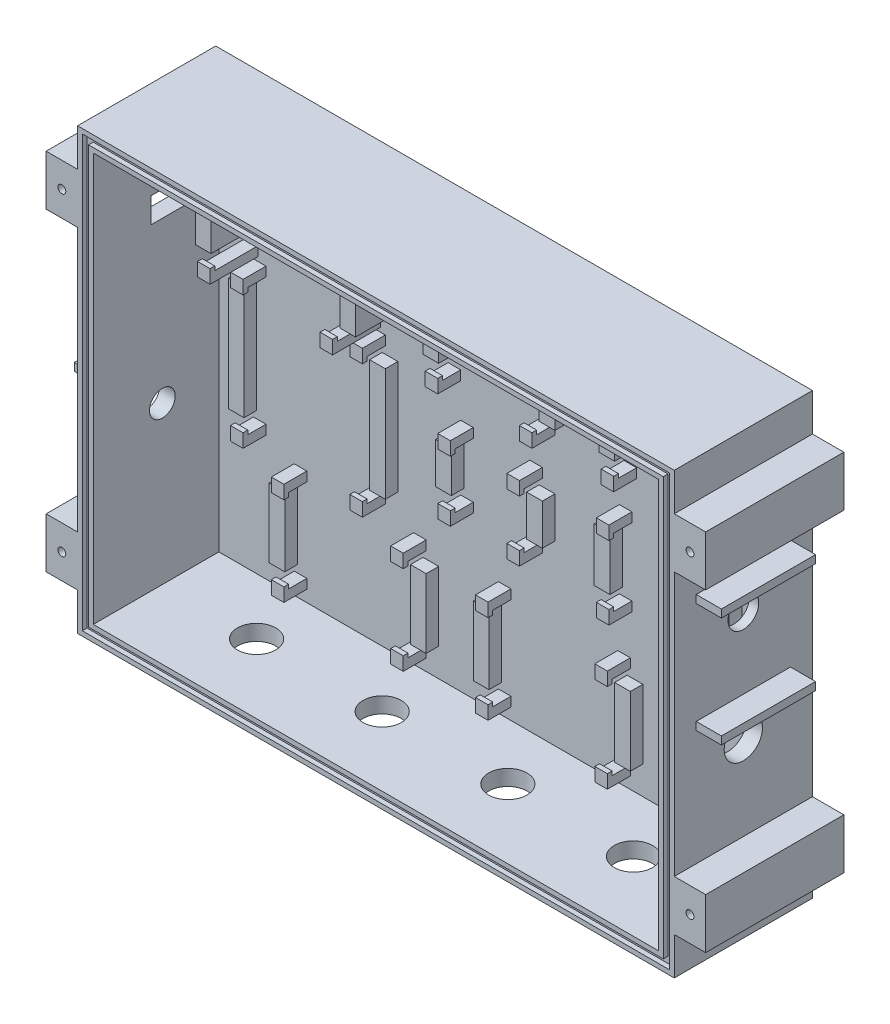
SolidWorks part; units mm, degrees
ref_plane "Front Plane" through (0, 0, 0) normal (0, 0, 1) x (1, 0, 0)
ref_plane "Top Plane" through (0, 0, 0) normal (0, 1, 0) x (1, 0, 0)
ref_plane "Right Plane" through (0, 0, 0) normal (1, 0, 0) x (0, 0, -1)
other "Configuration Table"
sketch "Sketch1" plane through (0, 0, 0) normal (0, 0, 1) x (1, 0, 0)
  line L0 (-95, -70) -> (95, -70)
  line L1 (95, -70) -> (95, 70)
  line L2 (95, 70) -> (-95, 70)
  line L3 (-95, 70) -> (-95, -70)
extrude "Box_Shell" add sketch "Sketch1" along normal blind 44
sketch "Sketch2" plane through (0, 0, 0) normal (0, 0, 1) x (1, 0, 0)
  line L0 (-90, -65) -> (90, -65)
  line L1 (90, -65) -> (90, 65)
  line L2 (90, 65) -> (-90, 65)
  line L3 (-90, 65) -> (-90, -65)
extrude "Box_Cavity" cut sketch "Sketch2" against normal blind 40 from offset 44
sketch "Sketch3" plane through (0, 0, 0) normal (0, 0, 1) x (1, 0, 0)
  line L0 (-105, -58) -> (-95, -58)
  line L1 (-95, -58) -> (-95, -42)
  line L2 (-95, -42) -> (-105, -42)
  line L3 (-105, -42) -> (-105, -58)
  line L4 (-105, 42) -> (-95, 42)
  line L5 (-95, 42) -> (-95, 58)
  line L6 (-95, 58) -> (-105, 58)
  line L7 (-105, 58) -> (-105, 42)
  line L8 (95, -58) -> (105, -58)
  line L9 (105, -58) -> (105, -42)
  line L10 (105, -42) -> (95, -42)
  line L11 (95, -42) -> (95, -58)
  line L12 (95, 42) -> (105, 42)
  line L13 (105, 42) -> (105, 58)
  line L14 (105, 58) -> (95, 58)
  line L15 (95, 58) -> (95, 42)
extrude "Lid_Lugs" add sketch "Sketch3" along normal blind 44
sketch "Sketch4" plane through (0, 0, 0) normal (0, 0, 1) x (1, 0, 0)
  circle A0 centre (-100, -50) radius 1.25
  circle A1 centre (-100, 50) radius 1.25
  circle A2 centre (100, -50) radius 1.25
  circle A3 centre (100, 50) radius 1.25
  dimension "D1" = 2.5
  dimension "D2" = 2.5
  dimension "D3" = 2.5
  dimension "D4" = 2.5
extrude "Lid_Screw_Holes_M3" cut sketch "Sketch4" against normal blind 12 from offset 44
sketch "Sketch5" plane through (0, 0, 0) normal (0, 0, 1) x (1, 0, 0)
  line L0 (-93.5, -68.5) -> (93.5, -68.5)
  line L1 (93.5, -68.5) -> (93.5, 68.5)
  line L2 (93.5, 68.5) -> (-93.5, 68.5)
  line L3 (-93.5, 68.5) -> (-93.5, -68.5)
  line L4 (-91.5, -66.5) -> (91.5, -66.5)
  line L5 (91.5, -66.5) -> (91.5, 66.5)
  line L6 (91.5, 66.5) -> (-91.5, 66.5)
  line L7 (-91.5, 66.5) -> (-91.5, -66.5)
extrude "Lid_Gasket_Groove" cut sketch "Sketch5" against normal blind 1.5 from offset 44
sketch "Sketch6" plane through (0, 0, 0) normal (0, 0, 1) x (1, 0, 0)
  line L0 (-85.5, 28) -> (-80.5, 28)
  line L1 (-80.5, 28) -> (-80.5, 52)
  line L2 (-80.5, 52) -> (-85.5, 52)
  line L3 (-85.5, 52) -> (-85.5, 28)
  line L4 (-39.5, 28) -> (-34.5, 28)
  line L5 (-34.5, 28) -> (-34.5, 52)
  line L6 (-34.5, 52) -> (-39.5, 52)
  line L7 (-39.5, 52) -> (-39.5, 28)
extrude "Pads_ESP32" add sketch "Sketch6" along normal blind 12 from offset 4
sketch "Sketch7" plane through (0, 0, 0) normal (0, 0, 1) x (1, 0, 0)
  line L0 (-81.5, 22.7) -> (-77.5, 22.7)
  line L1 (-77.5, 22.7) -> (-77.5, 25.7)
  line L2 (-77.5, 25.7) -> (-81.5, 25.7)
  line L3 (-81.5, 25.7) -> (-81.5, 22.7)
  line L4 (-81.5, 54.3) -> (-77.5, 54.3)
  line L5 (-77.5, 54.3) -> (-77.5, 57.3)
  line L6 (-77.5, 57.3) -> (-81.5, 57.3)
  line L7 (-81.5, 57.3) -> (-81.5, 54.3)
  line L8 (-42.5, 22.7) -> (-38.5, 22.7)
  line L9 (-38.5, 22.7) -> (-38.5, 25.7)
  line L10 (-38.5, 25.7) -> (-42.5, 25.7)
  line L11 (-42.5, 25.7) -> (-42.5, 22.7)
  line L12 (-42.5, 54.3) -> (-38.5, 54.3)
  line L13 (-38.5, 54.3) -> (-38.5, 57.3)
  line L14 (-38.5, 57.3) -> (-42.5, 57.3)
  line L15 (-42.5, 57.3) -> (-42.5, 54.3)
extrude "Clip_Posts_ESP32" add sketch "Sketch7" along normal blind 15.3 from offset 4
sketch "Sketch8" plane through (0, 0, 0) normal (0, 0, 1) x (1, 0, 0)
  line L0 (-81.5, 25.7) -> (-77.5, 25.7)
  line L1 (-77.5, 25.7) -> (-77.5, 27)
  line L2 (-77.5, 27) -> (-81.5, 27)
  line L3 (-81.5, 27) -> (-81.5, 25.7)
  line L4 (-81.5, 53) -> (-77.5, 53)
  line L5 (-77.5, 53) -> (-77.5, 54.3)
  line L6 (-77.5, 54.3) -> (-81.5, 54.3)
  line L7 (-81.5, 54.3) -> (-81.5, 53)
  line L8 (-42.5, 25.7) -> (-38.5, 25.7)
  line L9 (-38.5, 25.7) -> (-38.5, 27)
  line L10 (-38.5, 27) -> (-42.5, 27)
  line L11 (-42.5, 27) -> (-42.5, 25.7)
  line L12 (-42.5, 53) -> (-38.5, 53)
  line L13 (-38.5, 53) -> (-38.5, 54.3)
  line L14 (-38.5, 54.3) -> (-42.5, 54.3)
  line L15 (-42.5, 54.3) -> (-42.5, 53)
extrude "Clip_Lips_ESP32" add sketch "Sketch8" along normal blind 1.5 from offset 17.8
sketch "Sketch9" plane through (0, 0, 0) normal (0, 0, 1) x (1, 0, 0)
  line L0 (-21, 26) -> (-16, 26)
  line L1 (-16, 26) -> (-16, 54)
  line L2 (-16, 54) -> (-21, 54)
  line L3 (-21, 54) -> (-21, 26)
  line L4 (16, 26) -> (21, 26)
  line L5 (21, 26) -> (21, 54)
  line L6 (21, 54) -> (16, 54)
  line L7 (16, 54) -> (16, 26)
extrude "Pads_TDS" add sketch "Sketch9" along normal blind 4 from offset 4
sketch "Sketch10" plane through (0, 0, 0) normal (0, 0, 1) x (1, 0, 0)
  line L0 (-17, 20.7) -> (-13, 20.7)
  line L1 (-13, 20.7) -> (-13, 23.7)
  line L2 (-13, 23.7) -> (-17, 23.7)
  line L3 (-17, 23.7) -> (-17, 20.7)
  line L4 (-17, 56.3) -> (-13, 56.3)
  line L5 (-13, 56.3) -> (-13, 59.3)
  line L6 (-13, 59.3) -> (-17, 59.3)
  line L7 (-17, 59.3) -> (-17, 56.3)
  line L8 (13, 20.7) -> (17, 20.7)
  line L9 (17, 20.7) -> (17, 23.7)
  line L10 (17, 23.7) -> (13, 23.7)
  line L11 (13, 23.7) -> (13, 20.7)
  line L12 (13, 56.3) -> (17, 56.3)
  line L13 (17, 56.3) -> (17, 59.3)
  line L14 (17, 59.3) -> (13, 59.3)
  line L15 (13, 59.3) -> (13, 56.3)
extrude "Clip_Posts_TDS" add sketch "Sketch10" along normal blind 7.3 from offset 4
sketch "Sketch11" plane through (0, 0, 0) normal (0, 0, 1) x (1, 0, 0)
  line L0 (-17, 23.7) -> (-13, 23.7)
  line L1 (-13, 23.7) -> (-13, 25)
  line L2 (-13, 25) -> (-17, 25)
  line L3 (-17, 25) -> (-17, 23.7)
  line L4 (-17, 55) -> (-13, 55)
  line L5 (-13, 55) -> (-13, 56.3)
  line L6 (-13, 56.3) -> (-17, 56.3)
  line L7 (-17, 56.3) -> (-17, 55)
  line L8 (13, 23.7) -> (17, 23.7)
  line L9 (17, 23.7) -> (17, 25)
  line L10 (17, 25) -> (13, 25)
  line L11 (13, 25) -> (13, 23.7)
  line L12 (13, 55) -> (17, 55)
  line L13 (17, 55) -> (17, 56.3)
  line L14 (17, 56.3) -> (13, 56.3)
  line L15 (13, 56.3) -> (13, 55)
extrude "Clip_Lips_TDS" add sketch "Sketch11" along normal blind 1.5 from offset 9.8
sketch "Sketch12" plane through (0, 0, 0) normal (0, 0, 1) x (1, 0, 0)
  line L0 (35, 27) -> (40, 27)
  line L1 (40, 27) -> (40, 53)
  line L2 (40, 53) -> (35, 53)
  line L3 (35, 53) -> (35, 27)
  line L4 (70, 27) -> (75, 27)
  line L5 (75, 27) -> (75, 53)
  line L6 (75, 53) -> (70, 53)
  line L7 (70, 53) -> (70, 27)
extrude "Pads_ORP" add sketch "Sketch12" along normal blind 4 from offset 4
sketch "Sketch13" plane through (0, 0, 0) normal (0, 0, 1) x (1, 0, 0)
  line L0 (39, 21.7) -> (43, 21.7)
  line L1 (43, 21.7) -> (43, 24.7)
  line L2 (43, 24.7) -> (39, 24.7)
  line L3 (39, 24.7) -> (39, 21.7)
  line L4 (39, 55.3) -> (43, 55.3)
  line L5 (43, 55.3) -> (43, 58.3)
  line L6 (43, 58.3) -> (39, 58.3)
  line L7 (39, 58.3) -> (39, 55.3)
  line L8 (67, 21.7) -> (71, 21.7)
  line L9 (71, 21.7) -> (71, 24.7)
  line L10 (71, 24.7) -> (67, 24.7)
  line L11 (67, 24.7) -> (67, 21.7)
  line L12 (67, 55.3) -> (71, 55.3)
  line L13 (71, 55.3) -> (71, 58.3)
  line L14 (71, 58.3) -> (67, 58.3)
  line L15 (67, 58.3) -> (67, 55.3)
extrude "Clip_Posts_ORP" add sketch "Sketch13" along normal blind 7.3 from offset 4
sketch "Sketch14" plane through (0, 0, 0) normal (0, 0, 1) x (1, 0, 0)
  line L0 (39, 24.7) -> (43, 24.7)
  line L1 (43, 24.7) -> (43, 26)
  line L2 (43, 26) -> (39, 26)
  line L3 (39, 26) -> (39, 24.7)
  line L4 (39, 54) -> (43, 54)
  line L5 (43, 54) -> (43, 55.3)
  line L6 (43, 55.3) -> (39, 55.3)
  line L7 (39, 55.3) -> (39, 54)
  line L8 (67, 24.7) -> (71, 24.7)
  line L9 (71, 24.7) -> (71, 26)
  line L10 (71, 26) -> (67, 26)
  line L11 (67, 26) -> (67, 24.7)
  line L12 (67, 54) -> (71, 54)
  line L13 (71, 54) -> (71, 55.3)
  line L14 (71, 55.3) -> (67, 55.3)
  line L15 (67, 55.3) -> (67, 54)
extrude "Clip_Lips_ORP" add sketch "Sketch14" along normal blind 1.5 from offset 9.8
sketch "Sketch15" plane through (0, 0, 0) normal (0, 0, 1) x (1, 0, 0)
  line L0 (-83, -20) -> (-78, -20)
  line L1 (-78, -20) -> (-78, 16)
  line L2 (-78, 16) -> (-83, 16)
  line L3 (-83, 16) -> (-83, -20)
  line L4 (-38, -20) -> (-33, -20)
  line L5 (-33, -20) -> (-33, 16)
  line L6 (-33, 16) -> (-38, 16)
  line L7 (-38, 16) -> (-38, -20)
extrude "Pads_OPT" add sketch "Sketch15" along normal blind 4 from offset 4
sketch "Sketch16" plane through (0, 0, 0) normal (0, 0, 1) x (1, 0, 0)
  line L0 (-79, -25.3) -> (-75, -25.3)
  line L1 (-75, -25.3) -> (-75, -22.3)
  line L2 (-75, -22.3) -> (-79, -22.3)
  line L3 (-79, -22.3) -> (-79, -25.3)
  line L4 (-79, 18.3) -> (-75, 18.3)
  line L5 (-75, 18.3) -> (-75, 21.3)
  line L6 (-75, 21.3) -> (-79, 21.3)
  line L7 (-79, 21.3) -> (-79, 18.3)
  line L8 (-41, -25.3) -> (-37, -25.3)
  line L9 (-37, -25.3) -> (-37, -22.3)
  line L10 (-37, -22.3) -> (-41, -22.3)
  line L11 (-41, -22.3) -> (-41, -25.3)
  line L12 (-41, 18.3) -> (-37, 18.3)
  line L13 (-37, 18.3) -> (-37, 21.3)
  line L14 (-37, 21.3) -> (-41, 21.3)
  line L15 (-41, 21.3) -> (-41, 18.3)
extrude "Clip_Posts_OPT" add sketch "Sketch16" along normal blind 7.3 from offset 4
sketch "Sketch17" plane through (0, 0, 0) normal (0, 0, 1) x (1, 0, 0)
  line L0 (-79, -22.3) -> (-75, -22.3)
  line L1 (-75, -22.3) -> (-75, -21)
  line L2 (-75, -21) -> (-79, -21)
  line L3 (-79, -21) -> (-79, -22.3)
  line L4 (-79, 17) -> (-75, 17)
  line L5 (-75, 17) -> (-75, 18.3)
  line L6 (-75, 18.3) -> (-79, 18.3)
  line L7 (-79, 18.3) -> (-79, 17)
  line L8 (-41, -22.3) -> (-37, -22.3)
  line L9 (-37, -22.3) -> (-37, -21)
  line L10 (-37, -21) -> (-41, -21)
  line L11 (-41, -21) -> (-41, -22.3)
  line L12 (-41, 17) -> (-37, 17)
  line L13 (-37, 17) -> (-37, 18.3)
  line L14 (-37, 18.3) -> (-41, 18.3)
  line L15 (-41, 18.3) -> (-41, 17)
extrude "Clip_Lips_OPT" add sketch "Sketch17" along normal blind 1.5 from offset 9.8
sketch "Sketch18" plane through (0, 0, 0) normal (0, 0, 1) x (1, 0, 0)
  line L0 (-17, -8.5) -> (-12, -8.5)
  line L1 (-12, -8.5) -> (-12, 4.5)
  line L2 (-12, 4.5) -> (-17, 4.5)
  line L3 (-17, 4.5) -> (-17, -8.5)
  line L4 (12, -8.5) -> (17, -8.5)
  line L5 (17, -8.5) -> (17, 4.5)
  line L6 (17, 4.5) -> (12, 4.5)
  line L7 (12, 4.5) -> (12, -8.5)
extrude "Pads_MOSFET" add sketch "Sketch18" along normal blind 4 from offset 4
sketch "Sketch19" plane through (0, 0, 0) normal (0, 0, 1) x (1, 0, 0)
  line L0 (-13, -13.8) -> (-9, -13.8)
  line L1 (-9, -13.8) -> (-9, -10.8)
  line L2 (-9, -10.8) -> (-13, -10.8)
  line L3 (-13, -10.8) -> (-13, -13.8)
  line L4 (-13, 6.8) -> (-9, 6.8)
  line L5 (-9, 6.8) -> (-9, 9.8)
  line L6 (-9, 9.8) -> (-13, 9.8)
  line L7 (-13, 9.8) -> (-13, 6.8)
  line L8 (9, -13.8) -> (13, -13.8)
  line L9 (13, -13.8) -> (13, -10.8)
  line L10 (13, -10.8) -> (9, -10.8)
  line L11 (9, -10.8) -> (9, -13.8)
  line L12 (9, 6.8) -> (13, 6.8)
  line L13 (13, 6.8) -> (13, 9.8)
  line L14 (13, 9.8) -> (9, 9.8)
  line L15 (9, 9.8) -> (9, 6.8)
extrude "Clip_Posts_MOSFET" add sketch "Sketch19" along normal blind 7.3 from offset 4
sketch "Sketch20" plane through (0, 0, 0) normal (0, 0, 1) x (1, 0, 0)
  line L0 (-13, -10.8) -> (-9, -10.8)
  line L1 (-9, -10.8) -> (-9, -9.5)
  line L2 (-9, -9.5) -> (-13, -9.5)
  line L3 (-13, -9.5) -> (-13, -10.8)
  line L4 (-13, 5.5) -> (-9, 5.5)
  line L5 (-9, 5.5) -> (-9, 6.8)
  line L6 (-9, 6.8) -> (-13, 6.8)
  line L7 (-13, 6.8) -> (-13, 5.5)
  line L8 (9, -10.8) -> (13, -10.8)
  line L9 (13, -10.8) -> (13, -9.5)
  line L10 (13, -9.5) -> (9, -9.5)
  line L11 (9, -9.5) -> (9, -10.8)
  line L12 (9, 5.5) -> (13, 5.5)
  line L13 (13, 5.5) -> (13, 6.8)
  line L14 (13, 6.8) -> (9, 6.8)
  line L15 (9, 6.8) -> (9, 5.5)
extrude "Clip_Lips_MOSFET" add sketch "Sketch20" along normal blind 1.5 from offset 9.8
sketch "Sketch21" plane through (0, 0, 0) normal (0, 0, 1) x (1, 0, 0)
  line L0 (33.5, -10.5) -> (38.5, -10.5)
  line L1 (38.5, -10.5) -> (38.5, 6.5)
  line L2 (38.5, 6.5) -> (33.5, 6.5)
  line L3 (33.5, 6.5) -> (33.5, -10.5)
  line L4 (71.5, -10.5) -> (76.5, -10.5)
  line L5 (76.5, -10.5) -> (76.5, 6.5)
  line L6 (76.5, 6.5) -> (71.5, 6.5)
  line L7 (71.5, 6.5) -> (71.5, -10.5)
extrude "Pads_BUCK" add sketch "Sketch21" along normal blind 4 from offset 4
sketch "Sketch22" plane through (0, 0, 0) normal (0, 0, 1) x (1, 0, 0)
  line L0 (37.5, -15.8) -> (41.5, -15.8)
  line L1 (41.5, -15.8) -> (41.5, -12.8)
  line L2 (41.5, -12.8) -> (37.5, -12.8)
  line L3 (37.5, -12.8) -> (37.5, -15.8)
  line L4 (37.5, 8.8) -> (41.5, 8.8)
  line L5 (41.5, 8.8) -> (41.5, 11.8)
  line L6 (41.5, 11.8) -> (37.5, 11.8)
  line L7 (37.5, 11.8) -> (37.5, 8.8)
  line L8 (68.5, -15.8) -> (72.5, -15.8)
  line L9 (72.5, -15.8) -> (72.5, -12.8)
  line L10 (72.5, -12.8) -> (68.5, -12.8)
  line L11 (68.5, -12.8) -> (68.5, -15.8)
  line L12 (68.5, 8.8) -> (72.5, 8.8)
  line L13 (72.5, 8.8) -> (72.5, 11.8)
  line L14 (72.5, 11.8) -> (68.5, 11.8)
  line L15 (68.5, 11.8) -> (68.5, 8.8)
extrude "Clip_Posts_BUCK" add sketch "Sketch22" along normal blind 7.3 from offset 4
sketch "Sketch23" plane through (0, 0, 0) normal (0, 0, 1) x (1, 0, 0)
  line L0 (37.5, -12.8) -> (41.5, -12.8)
  line L1 (41.5, -12.8) -> (41.5, -11.5)
  line L2 (41.5, -11.5) -> (37.5, -11.5)
  line L3 (37.5, -11.5) -> (37.5, -12.8)
  line L4 (37.5, 7.5) -> (41.5, 7.5)
  line L5 (41.5, 7.5) -> (41.5, 8.8)
  line L6 (41.5, 8.8) -> (37.5, 8.8)
  line L7 (37.5, 8.8) -> (37.5, 7.5)
  line L8 (68.5, -12.8) -> (72.5, -12.8)
  line L9 (72.5, -12.8) -> (72.5, -11.5)
  line L10 (72.5, -11.5) -> (68.5, -11.5)
  line L11 (68.5, -11.5) -> (68.5, -12.8)
  line L12 (68.5, 7.5) -> (72.5, 7.5)
  line L13 (72.5, 7.5) -> (72.5, 8.8)
  line L14 (72.5, 8.8) -> (68.5, 8.8)
  line L15 (68.5, 8.8) -> (68.5, 7.5)
extrude "Clip_Lips_BUCK" add sketch "Sketch23" along normal blind 1.5 from offset 9.8
sketch "Sketch24" plane through (0, 0, 0) normal (0, 0, 1) x (1, 0, 0)
  line L0 (-70, -56) -> (-65, -56)
  line L1 (-65, -56) -> (-65, -34)
  line L2 (-65, -34) -> (-70, -34)
  line L3 (-70, -34) -> (-70, -56)
  line L4 (-25, -56) -> (-20, -56)
  line L5 (-20, -56) -> (-20, -34)
  line L6 (-20, -34) -> (-25, -34)
  line L7 (-25, -34) -> (-25, -56)
extrude "Pads_RELAY_RO" add sketch "Sketch24" along normal blind 4 from offset 4
sketch "Sketch25" plane through (0, 0, 0) normal (0, 0, 1) x (1, 0, 0)
  line L0 (-66, -61.3) -> (-62, -61.3)
  line L1 (-62, -61.3) -> (-62, -58.3)
  line L2 (-62, -58.3) -> (-66, -58.3)
  line L3 (-66, -58.3) -> (-66, -61.3)
  line L4 (-66, -31.7) -> (-62, -31.7)
  line L5 (-62, -31.7) -> (-62, -28.7)
  line L6 (-62, -28.7) -> (-66, -28.7)
  line L7 (-66, -28.7) -> (-66, -31.7)
  line L8 (-28, -61.3) -> (-24, -61.3)
  line L9 (-24, -61.3) -> (-24, -58.3)
  line L10 (-24, -58.3) -> (-28, -58.3)
  line L11 (-28, -58.3) -> (-28, -61.3)
  line L12 (-28, -31.7) -> (-24, -31.7)
  line L13 (-24, -31.7) -> (-24, -28.7)
  line L14 (-24, -28.7) -> (-28, -28.7)
  line L15 (-28, -28.7) -> (-28, -31.7)
extrude "Clip_Posts_RELAY_RO" add sketch "Sketch25" along normal blind 7.3 from offset 4
sketch "Sketch26" plane through (0, 0, 0) normal (0, 0, 1) x (1, 0, 0)
  line L0 (-66, -58.3) -> (-62, -58.3)
  line L1 (-62, -58.3) -> (-62, -57)
  line L2 (-62, -57) -> (-66, -57)
  line L3 (-66, -57) -> (-66, -58.3)
  line L4 (-66, -33) -> (-62, -33)
  line L5 (-62, -33) -> (-62, -31.7)
  line L6 (-62, -31.7) -> (-66, -31.7)
  line L7 (-66, -31.7) -> (-66, -33)
  line L8 (-28, -58.3) -> (-24, -58.3)
  line L9 (-24, -58.3) -> (-24, -57)
  line L10 (-24, -57) -> (-28, -57)
  line L11 (-28, -57) -> (-28, -58.3)
  line L12 (-28, -33) -> (-24, -33)
  line L13 (-24, -33) -> (-24, -31.7)
  line L14 (-24, -31.7) -> (-28, -31.7)
  line L15 (-28, -31.7) -> (-28, -33)
extrude "Clip_Lips_RELAY_RO" add sketch "Sketch26" along normal blind 1.5 from offset 9.8
sketch "Sketch27" plane through (0, 0, 0) normal (0, 0, 1) x (1, 0, 0)
  line L0 (-5, -56) -> (0, -56)
  line L1 (0, -56) -> (0, -34)
  line L2 (0, -34) -> (-5, -34)
  line L3 (-5, -34) -> (-5, -56)
  line L4 (40, -56) -> (45, -56)
  line L5 (45, -56) -> (45, -34)
  line L6 (45, -34) -> (40, -34)
  line L7 (40, -34) -> (40, -56)
extrude "Pads_RELAY_BYP" add sketch "Sketch27" along normal blind 4 from offset 4
sketch "Sketch28" plane through (0, 0, 0) normal (0, 0, 1) x (1, 0, 0)
  line L0 (-1, -61.3) -> (3, -61.3)
  line L1 (3, -61.3) -> (3, -58.3)
  line L2 (3, -58.3) -> (-1, -58.3)
  line L3 (-1, -58.3) -> (-1, -61.3)
  line L4 (-1, -31.7) -> (3, -31.7)
  line L5 (3, -31.7) -> (3, -28.7)
  line L6 (3, -28.7) -> (-1, -28.7)
  line L7 (-1, -28.7) -> (-1, -31.7)
  line L8 (37, -61.3) -> (41, -61.3)
  line L9 (41, -61.3) -> (41, -58.3)
  line L10 (41, -58.3) -> (37, -58.3)
  line L11 (37, -58.3) -> (37, -61.3)
  line L12 (37, -31.7) -> (41, -31.7)
  line L13 (41, -31.7) -> (41, -28.7)
  line L14 (41, -28.7) -> (37, -28.7)
  line L15 (37, -28.7) -> (37, -31.7)
extrude "Clip_Posts_RELAY_BYP" add sketch "Sketch28" along normal blind 7.3 from offset 4
sketch "Sketch29" plane through (0, 0, 0) normal (0, 0, 1) x (1, 0, 0)
  line L0 (-1, -58.3) -> (3, -58.3)
  line L1 (3, -58.3) -> (3, -57)
  line L2 (3, -57) -> (-1, -57)
  line L3 (-1, -57) -> (-1, -58.3)
  line L4 (-1, -33) -> (3, -33)
  line L5 (3, -33) -> (3, -31.7)
  line L6 (3, -31.7) -> (-1, -31.7)
  line L7 (-1, -31.7) -> (-1, -33)
  line L8 (37, -58.3) -> (41, -58.3)
  line L9 (41, -58.3) -> (41, -57)
  line L10 (41, -57) -> (37, -57)
  line L11 (37, -57) -> (37, -58.3)
  line L12 (37, -33) -> (41, -33)
  line L13 (41, -33) -> (41, -31.7)
  line L14 (41, -31.7) -> (37, -31.7)
  line L15 (37, -31.7) -> (37, -33)
extrude "Clip_Lips_RELAY_BYP" add sketch "Sketch29" along normal blind 1.5 from offset 9.8
sketch "Sketch30" plane through (0, 0, 0) normal (0, 1, 0) x (1, 0, 0)
  circle A0 centre (-60, -22) radius 6.1
  circle A1 centre (-20, -22) radius 6.1
  circle A2 centre (20, -22) radius 6.1
  circle A3 centre (60, -22) radius 6.1
  dimension "D1" = 12.2
  dimension "D2" = 12.2
  dimension "D3" = 12.2
  dimension "D4" = 12.2
extrude "Bottom_Gland_Holes" cut sketch "Sketch30" along normal blind 5.5 from offset 70.2 offset against normal yes
sketch "Sketch31" plane through (0, 0, 0) normal (1, 0, 0) x (0, 0, -1)
  circle A0 centre (-22, -15) radius 6.1
  dimension "D1" = 12.2
extrude "Right_Gland_Hole" cut sketch "Sketch31" against normal blind 5.5 from offset 95.2
sketch "Sketch32" plane through (0, 0, 0) normal (1, 0, 0) x (0, 0, -1)
  circle A0 centre (-22, 20) radius 4.9
  dimension "D1" = 9.8
extrude "BNC_Hole" cut sketch "Sketch32" against normal blind 5.5 from offset 95.2
sketch "Sketch33" plane through (0, 0, 0) normal (1, 0, 0) x (0, 0, -1)
  circle A0 centre (-22, 20) radius 8
  dimension "D1" = 16
extrude "BNC_Spot_Face" cut sketch "Sketch33" along normal blind 2 from offset 90
sketch "Sketch34" plane through (0, 0, 0) normal (1, 0, 0) x (0, 0, -1)
  circle A0 centre (-22, -15) radius 4.1
  dimension "D1" = 8.2
extrude "DC_Jack_Hole" cut sketch "Sketch34" along normal blind 5.5 from offset 95.2 offset against normal yes
sketch "Sketch35" plane through (0, 0, 0) normal (1, 0, 0) x (0, 0, -1)
  line L0 (-25.6, 36) -> (-12.6, 36)
  line L1 (-12.6, 36) -> (-12.6, 44)
  line L2 (-12.6, 44) -> (-25.6, 44)
  line L3 (-25.6, 44) -> (-25.6, 36)
extrude "USB_Slot" cut sketch "Sketch35" along normal blind 5.5 from offset 95.2 offset against normal yes
sketch "Sketch36" plane through (0, 0, 0) normal (0, 0, 1) x (1, 0, 0)
  line L0 (95, -5.25) -> (103, -5.25)
  line L1 (103, -5.25) -> (103, -2.75)
  line L2 (103, -2.75) -> (95, -2.75)
  line L3 (95, -2.75) -> (95, -5.25)
  line L4 (95, 29.75) -> (103, 29.75)
  line L5 (103, 29.75) -> (103, 32.25)
  line L6 (103, 32.25) -> (95, 32.25)
  line L7 (95, 32.25) -> (95, 29.75)
  line L8 (-103, -5.25) -> (-95, -5.25)
  line L9 (-95, -5.25) -> (-95, -2.75)
  line L10 (-95, -2.75) -> (-103, -2.75)
  line L11 (-103, -2.75) -> (-103, -5.25)
  line L12 (-103, 49.75) -> (-95, 49.75)
  line L13 (-95, 49.75) -> (-95, 52.25)
  line L14 (-95, 52.25) -> (-103, 52.25)
  line L15 (-103, 52.25) -> (-103, 49.75)
extrude "Drip_Lips" add sketch "Sketch36" along normal blind 30 from offset 7
sketch "Sketch37" plane through (0, 0, 0) normal (0, 0, 1) x (1, 0, 0)
  line L0 (-69, -78) -> (-51, -78)
  line L1 (-51, -78) -> (-51, -70)
  line L2 (-51, -70) -> (-69, -70)
  line L3 (-69, -70) -> (-69, -78)
  line L4 (-29, -78) -> (-11, -78)
  line L5 (-11, -78) -> (-11, -70)
  line L6 (-11, -70) -> (-29, -70)
  line L7 (-29, -70) -> (-29, -78)
  line L8 (11, -78) -> (29, -78)
  line L9 (29, -78) -> (29, -70)
  line L10 (29, -70) -> (11, -70)
  line L11 (11, -70) -> (11, -78)
  line L12 (51, -78) -> (69, -78)
  line L13 (69, -78) -> (69, -70)
  line L14 (69, -70) -> (51, -70)
  line L15 (51, -70) -> (51, -78)
extrude "Bottom_Drip_Shields" add sketch "Sketch37" along normal blind 2.5 from offset 31
equation "\"Jar_OD\"= 90  'ASSUMED - Part G fallback - jar outer diameter"
equation "\"Jar_H\"= 120  'ASSUMED - Part G fallback - jar height"
equation "\"Pump_L\"= 45  'ASSUMED - Part G fallback"
equation "\"Pump_W\"= 24  'ASSUMED - Part G fallback"
equation "\"Pump_H\"= 33  'ASSUMED - Part G fallback"
equation "\"Pump_Outlet_OD\"= 7.5  'ASSUMED - Part G fallback"
equation "\"Tube_OD\"= 8  'ASSUMED - Part G fallback"
equation "\"Tube_ID\"= 6  'ASSUMED - Part G fallback"
equation "\"TDS_Body_Dia\"= 12  'ASSUMED - Part G fallback"
equation "\"TDS_Wet_Len\"= 45  'ASSUMED - Part G fallback - length in water"
equation "\"DS_Tube_Dia\"= 6  'ASSUMED - Part G fallback"
equation "\"DS_Tube_Len\"= 50  'ASSUMED - Part G fallback"
equation "\"ORP_Body_Dia\"= 12  'ASSUMED - Part G fallback"
equation "\"ORP_Body_Len\"= 150  'ASSUMED - Part G fallback"
equation "\"ORP_Cap_Dia\"= 16  'ASSUMED - Part G fallback"
equation "\"Turb_W\"= 33  'ASSUMED - Part G fallback - head width"
equation "\"Turb_D\"= 28  'ASSUMED - Part G fallback - head depth"
equation "\"Turb_H\"= 30  'ASSUMED - Part G fallback - head height"
equation "\"Turb_Slot_W\"= 10  'ASSUMED - Part G fallback - slot width"
equation "\"Flow_L\"= 62  'ASSUMED - Part G fallback YF-S201"
equation "\"Flow_W\"= 36  'ASSUMED - Part G fallback"
equation "\"Flow_H\"= 35  'ASSUMED - Part G fallback"
equation "\"Thread_G12_OD\"= 20.955  'ASSUMED - Part G fallback thread G1/2 (major diameter)"
equation "\"Valve_L\"= 75  'ASSUMED - Part G fallback"
equation "\"Valve_W\"= 45  'ASSUMED - Part G fallback"
equation "\"Valve_H\"= 60  'ASSUMED - Part G fallback"
equation "\"Tee_L\"= 40  'ASSUMED - Part G fallback - overall length"
equation "\"Tee_Branch_L\"= 25  'ASSUMED - Part G fallback"
equation "\"Tee_OD\"= 12  'ASSUMED - Part G fallback"
equation "\"LED_Board_L\"= 20  'ASSUMED - Part G fallback"
equation "\"LED_Board_W\"= 20  'ASSUMED - Part G fallback - LED at centre"
equation "\"GUVA_L\"= 20  'ASSUMED - Part G fallback"
equation "\"GUVA_W\"= 12  'ASSUMED - Part G fallback - sensor at centre"
equation "\"Reed_L\"= 27  'ASSUMED - Part G fallback MC-38 half"
equation "\"Reed_W\"= 14  'ASSUMED - Part G fallback"
equation "\"Reed_H\"= 8  'ASSUMED - Part G fallback"
equation "\"ESP_L\"= 51  'ASSUMED - Part G fallback"
equation "\"ESP_W\"= 28  'ASSUMED - Part G fallback"
equation "\"TFT_L\"= 58  'ASSUMED - Part G fallback - board"
equation "\"TFT_W\"= 35  'ASSUMED - Part G fallback - board"
equation "\"TFT_Win_L\"= 35  'ASSUMED - Part G fallback - visible window"
equation "\"TFT_Win_W\"= 28  'ASSUMED - Part G fallback - visible window"
equation "\"Relay_L\"= 50  'ASSUMED - Part G fallback"
equation "\"Relay_W\"= 26  'ASSUMED - Part G fallback"
equation "\"Relay_H\"= 19  'ASSUMED - Part G fallback"
equation "\"Mosfet_L\"= 34  'ASSUMED - Part G fallback"
equation "\"Mosfet_W\"= 17  'ASSUMED - Part G fallback"
equation "\"Mosfet_H\"= 12  'ASSUMED - Part G fallback"
equation "\"TDS_Board_L\"= 42  'ASSUMED - Part G fallback"
equation "\"TDS_Board_W\"= 32  'ASSUMED - Part G fallback"
equation "\"Turb_Board_L\"= 38  'ASSUMED - Part G fallback"
equation "\"Turb_Board_W\"= 28  'ASSUMED - Part G fallback"
equation "\"BNC_Thread_Dia\"= 9.5  'ASSUMED - Part G fallback"
equation "\"Plate_L\"= 420  'ASSUMED - Part G fallback"
equation "\"Plate_W\"= 297  'ASSUMED - Part G fallback"
equation "\"Plate_T\"= 6  'ASSUMED - Part G fallback"
equation "\"Booster_L\"= 150  'ASSUMED - Part G fallback - booster pump"
equation "\"Booster_W\"= 95  'ASSUMED - Part G fallback"
equation "\"Booster_H\"= 100  'ASSUMED - Part G fallback"
equation "\"PTube_OD\"= 6.35  'ASSUMED - Part G fallback - product tube 1/4 inch"
equation "\"Qz_Out\"= 12  'ASSUMED - Part G fallback - quartz channel outside square"
equation "\"Qz_Path\"= 10  'ASSUMED - Part G fallback - quartz channel inside light path"
equation "\"Qz_L\"= 40  'ASSUMED - Part G fallback - quartz channel length"
equation "\"LED860_Dia\"= 5  'ASSUMED - Part G fallback - 860 nm LED"
equation "\"BPW_L\"= 5.4  'ASSUMED - Part G fallback - BPW34"
equation "\"BPW_W\"= 4.3  'ASSUMED - Part G fallback - BPW34"
equation "\"Cart_Dia\"= 50  'ASSUMED - Part G fallback - sediment and pre-carbon cartridges"
equation "\"Cart_L\"= 255  'ASSUMED - Part G fallback"
equation "\"UF_Dia\"= 50  'ASSUMED - Part G fallback - UF cartridge"
equation "\"UF_L\"= 260  'ASSUMED - Part G fallback"
equation "\"RO_Dia\"= 62  'ASSUMED - Part G fallback - RO membrane housing"
equation "\"RO_L\"= 300  'ASSUMED - Part G fallback"
equation "\"UVC_Dia\"= 40  'ASSUMED - Part G fallback - UV-C chamber"
equation "\"UVC_L\"= 300  'ASSUMED - Part G fallback"
equation "\"Tank_W\"= 260  'ASSUMED - Part G fallback - storage tank"
equation "\"Tank_D\"= 160  'ASSUMED - Part G fallback"
equation "\"Tank_H\"= 300  'ASSUMED - Part G fallback"
equation "\"Cab_W\"= 400  'ASSUMED - Part G fallback - purifier cabinet"
equation "\"Cab_D\"= 270  'ASSUMED - Part G fallback"
equation "\"Cab_H\"= 560  'ASSUMED - Part G fallback"
equation "\"ORP_Board_L\"= 40  'ASSUMED - Part G fallback - ORP buffer board"
equation "\"ORP_Board_W\"= 30  'ASSUMED - Part G fallback"
equation "\"Opt_Board_L\"= 50  'ASSUMED - Part G fallback - optical front-end board"
equation "\"Opt_Board_W\"= 40  'ASSUMED - Part G fallback"
equation "\"Buck_L\"= 43  'ASSUMED - Part G fallback - 12 V to 5 V buck module"
equation "\"Buck_W\"= 21  'ASSUMED - Part G fallback"
equation "\"Buck_H\"= 14  'ASSUMED - Part G fallback"
equation "\"BB_L\"= 165  'ASSUMED - Part G fallback - breadboard (As_Built_R3 only)"
equation "\"BB_W\"= 55  'ASSUMED - Part G fallback"
equation "\"BB_H\"= 10  'ASSUMED - Part G fallback"
equation "\"Cuv_W\"= 12.5  'ASSUMED - old R3 cuvette (station suppressed in SS4)"
equation "\"Cuv_D\"= 12.5  'ASSUMED - old R3 cuvette (station suppressed in SS4)"
equation "\"Cuv_H\"= 45  'ASSUMED - old R3 cuvette (station suppressed in SS4)"
equation "\"Probe_Clr\"= 0.3  'DESIGN VALUE - Part C rule 3 - printed probe hole = diameter + 0.3"
equation "\"Label_H\"= 0.6  'DESIGN VALUE - Part D - raised label height"
